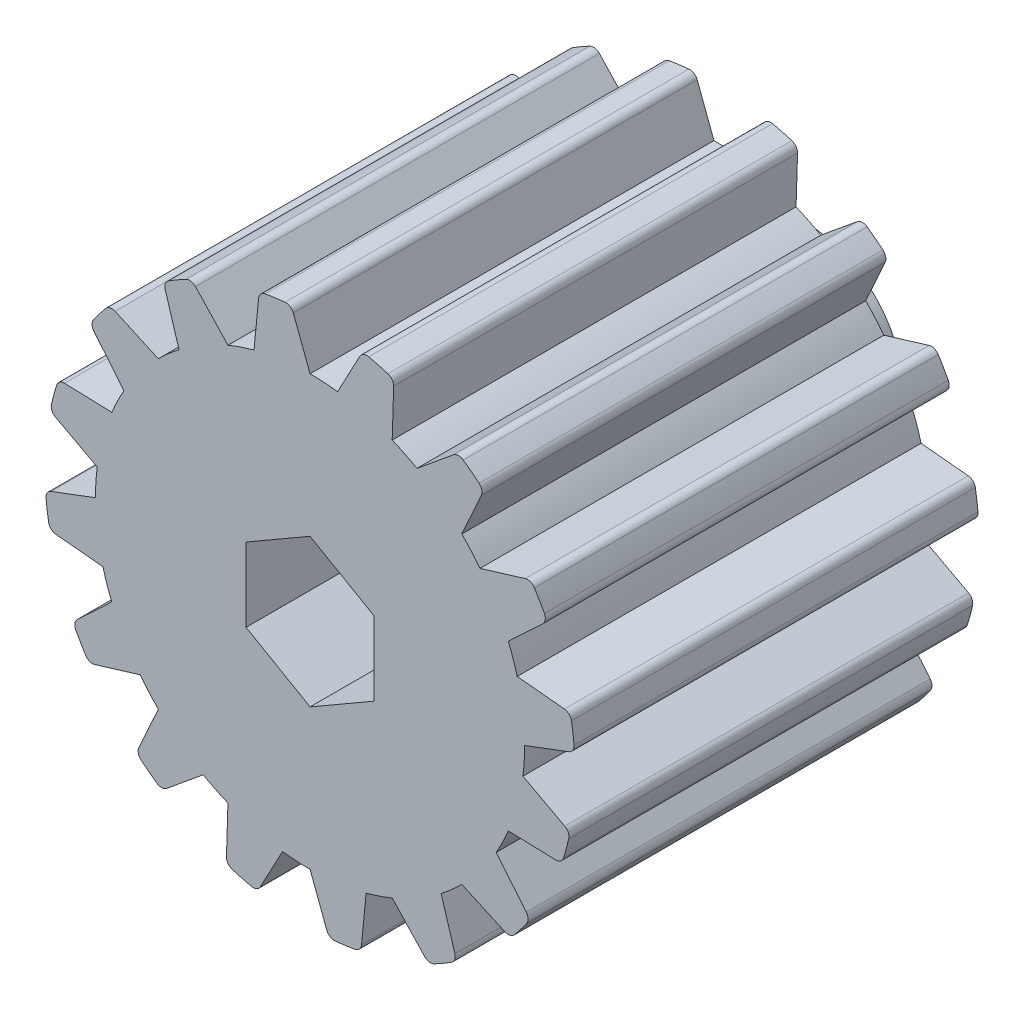
SolidWorks part; units mm, degrees
ref_plane "Alzado" through (0, 0, 0) normal (0, 0, 1) x (1, 0, 0)
ref_plane "Planta" through (0, 0, 0) normal (0, 1, 0) x (1, 0, 0)
ref_plane "Vista lateral" through (0, 0, 0) normal (1, 0, 0) x (0, 0, -1)
sketch "Croquis2" plane through (0, 0, 0) normal (0, 0, 1) x (1, 0, 0)
  line L0 (0, 0) -> (0, 7.9702) construction
  line L2 (-2.0817, 7.6936) -> (-1.9112, 9.4453)
  line L3 (-1.0408, 7.8319) -> (0, 0) construction
  line L4 (0, 7.9702) -> (-0.6221, 9.6166)
  line L5 (1.021, 7.9046) -> (1.8489, 9.4577)
  line L6 (3.0501, 7.3635) -> (3.1053, 9.1227)
  line L7 (3.9682, 6.9122) -> (5.3274, 8.0302)
  line L8 (5.6358, 5.6358) -> (6.3601, 7.2399)
  line L9 (6.3113, 4.8674) -> (7.9949, 5.3803)
  line L10 (7.3635, 3.0501) -> (8.6465, 4.2549)
  line L11 (7.6936, 2.0817) -> (9.4453, 1.9112)
  line L12 (7.9702, 0) -> (9.6166, 0.6221)
  line L13 (7.9046, -1.021) -> (9.4577, -1.8489)
  line L14 (7.3635, -3.0501) -> (9.1227, -3.1053)
  line L15 (6.9122, -3.9682) -> (8.0302, -5.3274)
  line L16 (5.6358, -5.6358) -> (7.2399, -6.3601)
  line L17 (4.8674, -6.3113) -> (5.3803, -7.9949)
  line L18 (3.0501, -7.3635) -> (4.2549, -8.6465)
  line L19 (2.0817, -7.6936) -> (1.9112, -9.4453)
  line L20 (0, -7.9702) -> (0.6221, -9.6166)
  line L21 (-1.021, -7.9046) -> (-1.8489, -9.4577)
  line L22 (-3.0501, -7.3635) -> (-3.1053, -9.1227)
  line L23 (-3.9682, -6.9122) -> (-5.3274, -8.0302)
  line L24 (-5.6358, -5.6358) -> (-6.3601, -7.2399)
  line L25 (-6.3113, -4.8674) -> (-7.9949, -5.3803)
  line L26 (-7.3635, -3.0501) -> (-8.6465, -4.2549)
  line L27 (-7.6936, -2.0817) -> (-9.4453, -1.9112)
  line L28 (-7.9702, 0) -> (-9.6166, -0.6221)
  line L29 (-7.9046, 1.021) -> (-9.4577, 1.8489)
  line L30 (-7.3635, 3.0501) -> (-9.1227, 3.1053)
  line L31 (-6.9122, 3.9682) -> (-8.0302, 5.3274)
  line L32 (-5.6358, 5.6358) -> (-7.2399, 6.3601)
  line L33 (-4.8674, 6.3113) -> (-5.3803, 7.9949)
  line L34 (-3.0501, 7.3635) -> (-4.2549, 8.6465)
  arc A0 (-4.8674, 6.3113) -> (-5.6358, 5.6358) centre (0, 0) ccw
  arc A1 (-7.5914, 6.2764) -> (-8.0413, 5.6886) centre (0, 0) ccw
  arc A2 (-1.6636, 9.7085) -> (-1.9112, 9.4453) centre (-1.6129, 9.4128) ccw
  arc A3 (-0.9298, 9.806) -> (-0.6221, 9.6166) centre (-0.9015, 9.5074) cw
  arc A4 (2.1783, 9.6061) -> (1.8489, 9.4577) centre (2.112, 9.3135) ccw
  arc A5 (2.8935, 9.4154) -> (3.1053, 9.1227) centre (2.8054, 9.1286) cw
  arc A6 (5.6886, 8.0413) -> (5.3274, 8.0302) centre (5.5153, 7.7964) ccw
  arc A7 (6.2764, 7.5914) -> (6.3601, 7.2399) centre (6.0852, 7.3602) cw
  arc A8 (8.3328, 5.2523) -> (7.9949, 5.3803) centre (8.0791, 5.0923) ccw
  arc A9 (8.7037, 4.6117) -> (8.6465, 4.2549) centre (8.4387, 4.4712) cw
  arc A10 (9.7085, 1.6636) -> (9.4453, 1.9112) centre (9.4128, 1.6129) ccw
  arc A11 (9.806, 0.9298) -> (9.6166, 0.6221) centre (9.5074, 0.9015) cw
  arc A12 (9.6061, -2.1783) -> (9.4577, -1.8489) centre (9.3135, -2.112) ccw
  arc A13 (9.4154, -2.8935) -> (9.1227, -3.1053) centre (9.1286, -2.8054) cw
  arc A14 (8.0413, -5.6886) -> (8.0302, -5.3274) centre (7.7964, -5.5153) ccw
  arc A15 (7.5914, -6.2764) -> (7.2399, -6.3601) centre (7.3602, -6.0852) cw
  arc A16 (5.2523, -8.3328) -> (5.3803, -7.9949) centre (5.0923, -8.0791) ccw
  arc A17 (4.6117, -8.7037) -> (4.2549, -8.6465) centre (4.4712, -8.4387) cw
  arc A18 (1.6636, -9.7085) -> (1.9112, -9.4453) centre (1.6129, -9.4128) ccw
  arc A19 (0.9298, -9.806) -> (0.6221, -9.6166) centre (0.9015, -9.5074) cw
  arc A20 (-2.1783, -9.6061) -> (-1.8489, -9.4577) centre (-2.112, -9.3135) ccw
  arc A21 (-2.8935, -9.4154) -> (-3.1053, -9.1227) centre (-2.8054, -9.1286) cw
  arc A22 (-5.6886, -8.0413) -> (-5.3274, -8.0302) centre (-5.5153, -7.7964) ccw
  arc A23 (-6.2764, -7.5914) -> (-6.3601, -7.2399) centre (-6.0852, -7.3602) cw
  arc A24 (-8.3328, -5.2523) -> (-7.9949, -5.3803) centre (-8.0791, -5.0923) ccw
  arc A25 (-8.7037, -4.6117) -> (-8.6465, -4.2549) centre (-8.4387, -4.4712) cw
  arc A26 (-9.7085, -1.6636) -> (-9.4453, -1.9112) centre (-9.4128, -1.6129) ccw
  arc A27 (-9.806, -0.9298) -> (-9.6166, -0.6221) centre (-9.5074, -0.9015) cw
  arc A28 (-9.6061, 2.1783) -> (-9.4577, 1.8489) centre (-9.3135, 2.112) ccw
  arc A29 (-9.4154, 2.8935) -> (-9.1227, 3.1053) centre (-9.1286, 2.8054) cw
  arc A30 (-8.0413, 5.6886) -> (-8.0302, 5.3274) centre (-7.7964, 5.5153) ccw
  arc A31 (-7.5914, 6.2764) -> (-7.2399, 6.3601) centre (-7.3602, 6.0852) cw
  arc A32 (-5.2523, 8.3328) -> (-5.3803, 7.9949) centre (-5.0923, 8.0791) ccw
  arc A33 (-4.6117, 8.7037) -> (-4.2549, 8.6465) centre (-4.4712, 8.4387) cw
  arc A34 (-4.6117, 8.7037) -> (-5.2523, 8.3328) centre (0, 0) ccw
  arc A35 (-0.9298, 9.806) -> (-1.6636, 9.7085) centre (0, 0) ccw
  arc A36 (2.8935, 9.4154) -> (2.1783, 9.6061) centre (0, 0) ccw
  arc A37 (6.2764, 7.5914) -> (5.6886, 8.0413) centre (0, 0) ccw
  arc A38 (8.7037, 4.6117) -> (8.3328, 5.2523) centre (0, 0) ccw
  arc A39 (9.4154, -2.8935) -> (9.6061, -2.1783) centre (0, 0) ccw
  arc A40 (7.5914, -6.2764) -> (8.0413, -5.6886) centre (0, 0) ccw
  arc A41 (-9.4154, 2.8935) -> (-9.6061, 2.1783) centre (0, 0) ccw
  arc A42 (-9.806, -0.9298) -> (-9.7085, -1.6636) centre (0, 0) ccw
  arc A43 (-8.7037, -4.6117) -> (-8.3328, -5.2523) centre (0, 0) ccw
  arc A44 (-6.2764, -7.5914) -> (-5.6886, -8.0413) centre (0, 0) ccw
  arc A45 (-2.8935, -9.4154) -> (-2.1783, -9.6061) centre (0, 0) ccw
  arc A46 (0.9298, -9.806) -> (1.6636, -9.7085) centre (0, 0) ccw
  arc A47 (4.6117, -8.7037) -> (5.2523, -8.3328) centre (0, 0) ccw
  arc A48 (-2.0817, 7.6936) -> (-3.0501, 7.3635) centre (0, 0) ccw
  arc A49 (1.021, 7.9046) -> (0, 7.9702) centre (0, 0) ccw
  arc A50 (3.9682, 6.9122) -> (3.0501, 7.3635) centre (0, 0) ccw
  arc A51 (6.3113, 4.8674) -> (5.6358, 5.6358) centre (0, 0) ccw
  arc A52 (7.6936, 2.0817) -> (7.3635, 3.0501) centre (0, 0) ccw
  arc A53 (7.9046, -1.021) -> (7.9702, 0) centre (0, 0) ccw
  arc A54 (9.806, 0.9298) -> (9.7085, 1.6636) centre (0, 0) ccw
  arc A55 (6.9122, -3.9682) -> (7.3635, -3.0501) centre (0, 0) ccw
  arc A56 (4.8674, -6.3113) -> (5.6358, -5.6358) centre (0, 0) ccw
  arc A57 (2.0817, -7.6936) -> (3.0501, -7.3635) centre (0, 0) ccw
  arc A58 (-1.021, -7.9046) -> (0, -7.9702) centre (0, 0) ccw
  arc A59 (-3.9682, -6.9122) -> (-3.0501, -7.3635) centre (0, 0) ccw
  arc A60 (-6.3113, -4.8674) -> (-5.6358, -5.6358) centre (0, 0) ccw
  arc A61 (-7.6936, -2.0817) -> (-7.3635, -3.0501) centre (0, 0) ccw
  arc A62 (-7.9046, 1.021) -> (-7.9702, 0) centre (0, 0) ccw
  arc A63 (-6.9122, 3.9682) -> (-7.3635, 3.0501) centre (0, 0) ccw
  dimension "D1" = 2.1
  dimension "D2" = 19.7
  dimension "D3" = 15.9404
  dimension "D6" = 0.6
  dimension "D4" = 1.76
extrude "Saliente-Extruir1" add sketch "Croquis2" along normal blind 15
sketch "Croquis5" plane through (0, 0, 0) normal (0, 0, -1) x (-1, 0, 0)
  circle A0 centre (0, 0) radius 4.5
  dimension "D1" = 9
extrude "Saliente-Extruir2" add sketch "Croquis5" along normal blind 6
scale "Escala1" scale about origin uniform scaling yes scale factor 1.5
sketch "Croquis7" plane through (0, 0, -9) normal (0, 0, -1) x (-1, 0, 0)
  circle A0 centre (0, 0) radius 10
  dimension "D1" = 20
extrude "Cortar-Extruir3" cut sketch "Croquis7" against normal blind 5.8 and the other way through all
sketch "Croquis8" plane through (0, 0, -3.2) normal (0, 0, -1) x (-1, 0, 0)
  circle A3 centre (0, 0) radius 5.5
  dimension "D1" = 11
extrude "Saliente-Extruir3" add sketch "Croquis8" along normal blind 1.87
sketch "Croquis10" plane through (0, 0, 22.5) normal (0, 0, 1) x (1, 0, 0)
  line L0 (0, 4) -> (0, -5.201) construction
  line L1 (0, 4) -> (-3.4641, 2) construction
  line L2 (-3.4641, 2) -> (-3.4641, -2) construction
  line L3 (-3.4641, -2) -> (0, -4) construction
  line L4 (0, -4) -> (3.4641, -2) construction
  line L5 (3.4641, -2) -> (3.4641, 2) construction
  line L6 (3.4641, 2) -> (0, 4) construction
  line L8 (0, 4.1155) -> (-3.5641, 2.0577)
  line L9 (-3.5641, 2.0577) -> (-3.5641, -2.0577)
  line L10 (-3.5641, -2.0577) -> (0, -4.1155)
  line L11 (0, -4.1155) -> (3.5641, -2.0577)
  line L12 (3.5641, -2.0577) -> (3.5641, 2.0577)
  line L13 (3.5641, 2.0577) -> (0, 4.1155)
  circle A0 centre (0, 0) radius 4 construction
  circle A1 centre (0, 0) radius 4 construction
  circle A3 centre (0, 0) radius 3.5641 construction
  dimension "D1" = 8
  dimension "D2" = 0.1
extrude "Cortar-Extruir4" cut sketch "Croquis10" against normal through all both and the other way through all
sketch "Croquis11" plane through (0, 0, 22.5) normal (0, 0, 1) x (1, 0, 0)
  circle A0 centre (0, 0) radius 13.745
  dimension "D1" = 27.49
